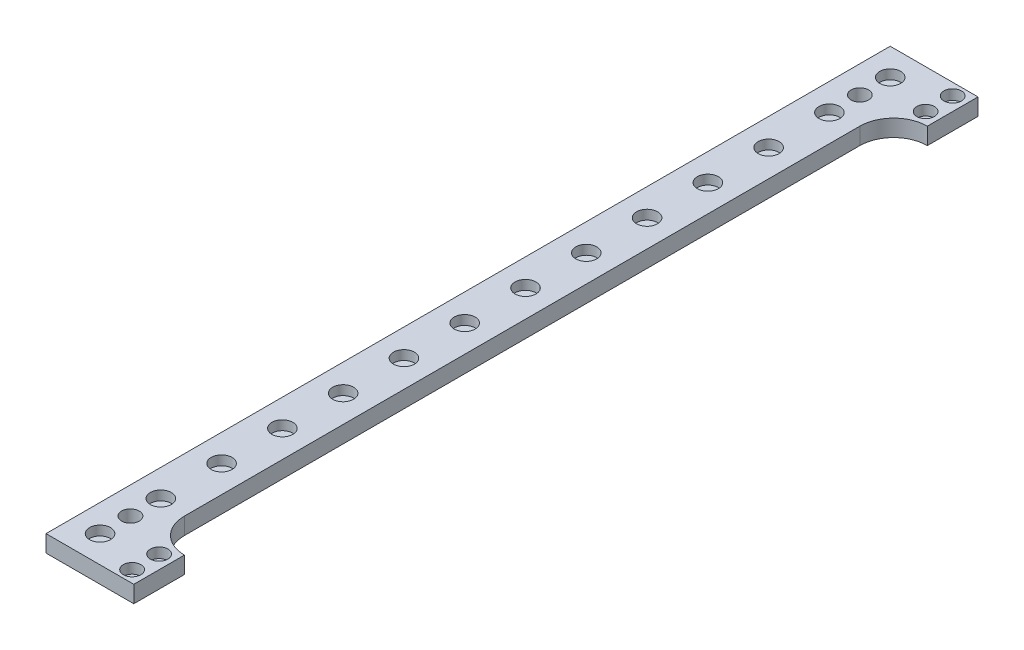
SolidWorks part; units mm, degrees
ref_plane "Front Plane" through (0, 0, 0) normal (0, 0, 1) x (1, 0, 0)
ref_plane "Top Plane" through (0, 0, 0) normal (0, 1, 0) x (1, 0, 0)
ref_plane "Right Plane" through (0, 0, 0) normal (1, 0, 0) x (0, 0, -1)
sketch "Sketch1" plane through (0, 0, 0) normal (0, 1, 0) x (1, 0, 0)
  line L1 (0, 0) -> (16, 0)
  line L2 (0, 0) -> (0, 250)
  line L3 (0, 250) -> (16, 250)
  line L4 (16, 0) -> (16, 250)
  dimension "D1" = 16
  dimension "D2" = 250
extrude "Boss-Extrude1" add sketch "Sketch1" along normal blind 5
sketch "Sketch2" plane through (0, 5, 0) normal (0, 1, 0) x (1, 0, 0)
  line L0 (8, 250) -> (8, 0) construction
  line L1 (16, 250) -> (0, 250) construction
  line L2 (0, 0) -> (16, 0) construction
  circle A0 centre (8, 242) radius 3.1
  circle A1 centre (8, 224) radius 3.1
  circle A2 centre (8, 206) radius 3.1
  circle A3 centre (8, 188) radius 3.1
  circle A4 centre (8, 170) radius 3.1
  circle A5 centre (8, 152) radius 3.1
  circle A6 centre (8, 134) radius 3.1
  circle A7 centre (8, 116) radius 3.1
  circle A8 centre (8, 98) radius 3.1
  circle A9 centre (8, 80) radius 3.1
  circle A10 centre (8, 62) radius 3.1
  circle A11 centre (8, 44) radius 3.1
  circle A12 centre (8, 26) radius 3.1
  circle A13 centre (8, 8) radius 3.1
  dimension "D1" = 6.2
  dimension "D3" = 8
  dimension "D2" = 14
extrude "Cut-Extrude1" cut sketch "Sketch2" against normal blind 2.8
sketch "Sketch4" plane through (0, 5, 0) normal (0, 1, 0) x (1, 0, 0)
  line L0 (16, 0) -> (16, 250) construction
  line L1 (16, 0) -> (26, 0)
  line L2 (16, 0) -> (16, 15)
  line L3 (16, 15) -> (26, 15)
  line L4 (26, 0) -> (26, 15)
  line L6 (16, 235) -> (26, 235)
  line L7 (16, 235) -> (16, 250)
  line L8 (16, 250) -> (26, 250)
  line L9 (26, 235) -> (26, 250)
  line L11 (16, 250) -> (0, 250) construction
  line L12 (0, 0) -> (16, 0) construction
  dimension "D3" = 15
  dimension "D4" = 15
  dimension "D5" = 10
  dimension "D6" = 10
extrude "Boss-Extrude2" add sketch "Sketch4" against normal up to surface (5 mm away) up to face at (8, 0, -125)
sketch "Sketch5" plane through (0, 0, 0) normal (0, -1, 0) x (1, 0, 0)
  line L0 (22, 0) -> (22, -250) construction
  line L1 (0, 0) -> (26, 0) construction
  line L2 (26, -250) -> (0, -250) construction
  line L3 (26, -15) -> (16, -15) construction
  line L5 (26, -235) -> (26, -250) construction
  line L6 (8, -242) -> (8, -8) construction
  circle A0 centre (22, -3.5) radius 1.65
  circle A1 centre (22, -11.5) radius 1.65
  circle A2 centre (22, -238.5) radius 1.65
  circle A3 centre (22, -246.5) radius 1.65
  circle A4 centre (8, -17) radius 1.65
  circle A5 centre (8, -233) radius 1.65
  point P26 (0, 0)
  point P27 (0, 0)
  dimension "D1" = 3.3
  dimension "D2" = 8
  dimension "D3" = 3.5
  dimension "D4" = 8
  dimension "D5" = 3.5
  dimension "D6" = 4
  dimension "D7" = 9
  dimension "D8" = 9
extrude "Cut-Extrude2" cut sketch "Sketch5" against normal up to next
sketch "Sketch6" plane through (0, 5, 0) normal (0, 1, 0) x (1, 0, 0)
  circle A0 centre (22, 246.5) radius 2.6
  circle A1 centre (22, 238.5) radius 2.6
  circle A2 centre (22, 11.5) radius 2.6
  circle A3 centre (22, 3.5) radius 2.6
  circle A4 centre (8, 233) radius 2.6
  circle A5 centre (8, 17) radius 2.6
  dimension "D1" = 5.2
extrude "Cut-Extrude3" cut sketch "Sketch6" against normal blind 3
fillet "Fillet1" radius 10 2 edges at (16, 2.5, -235) (16, 2.5, -15)
sketch "Sketch8" plane through (0, 5, 0) normal (0, 1, 0) x (1, 0, 0)
  circle A0 centre (8, 233) radius 2.6
  circle A1 centre (8, 17) radius 2.6
extrude "Cut-Extrude4" cut sketch "Sketch8" against normal blind 4
